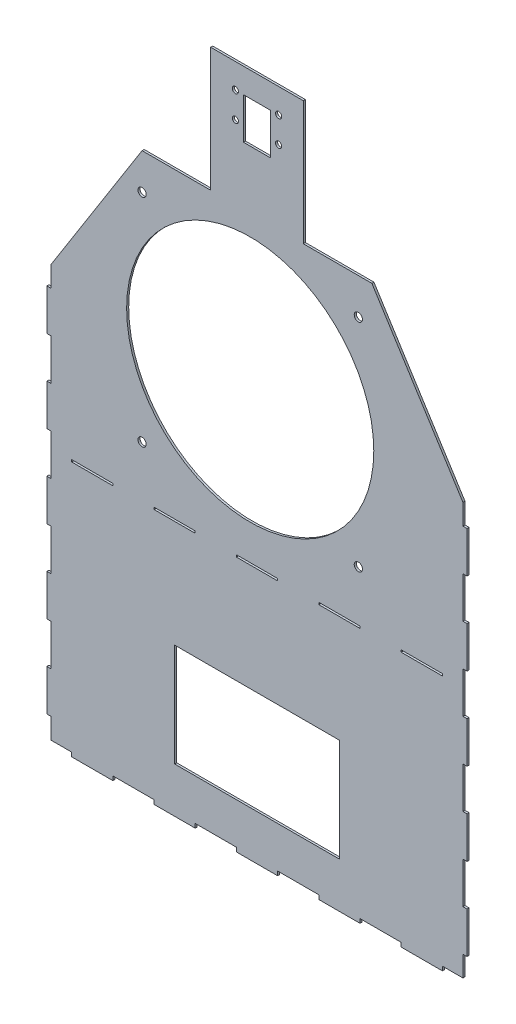
SolidWorks part; units mm, degrees
ref_plane "Přední rovina" through (0, 0, 0) normal (0, 0, 1) x (1, 0, 0)
ref_plane "Horní rovina" through (0, 0, 0) normal (0, 1, 0) x (1, 0, 0)
ref_plane "Pravá rovina" through (0, 0, 0) normal (1, 0, 0) x (0, 0, -1)
sketch "Skica1" plane through (0, 0, 0) normal (0, 0, 1) x (1, 0, 0)
  line L0 (-24.5981, -113.24) -> (-24.5981, -95.4761)
  line L1 (-124.5981, -113.24) -> (75.4019, -113.24)
  line L2 (-124.5981, -113.24) -> (-124.5981, 156.76)
  line L3 (-124.5981, 156.76) -> (75.4019, 156.76)
  line L4 (75.4019, -113.24) -> (75.4019, 156.76)
  line L5 (-114.5981, -113.24) -> (-94.5981, -113.24)
  line L6 (-114.5981, -113.24) -> (-114.5981, -115.24)
  line L7 (-114.5981, -115.24) -> (-94.5981, -115.24)
  line L8 (-94.5981, -113.24) -> (-94.5981, -115.24)
  line L9 (-74.5981, -113.24) -> (-54.5981, -113.24)
  line L10 (-74.5981, -113.24) -> (-74.5981, -115.24)
  line L11 (-74.5981, -115.24) -> (-54.5981, -115.24)
  line L12 (-54.5981, -113.24) -> (-54.5981, -115.24)
  line L13 (-34.5981, -113.24) -> (-14.5981, -113.24)
  line L14 (-34.5981, -113.24) -> (-34.5981, -115.24)
  line L15 (-34.5981, -115.24) -> (-14.5981, -115.24)
  line L16 (-14.5981, -113.24) -> (-14.5981, -115.24)
  line L17 (25.4019, -115.24) -> (5.4019, -115.24)
  line L18 (5.4019, -113.24) -> (5.4019, -115.24)
  line L19 (25.4019, -113.24) -> (5.4019, -113.24)
  line L20 (25.4019, -113.24) -> (25.4019, -115.24)
  line L21 (65.4019, -115.24) -> (45.4019, -115.24)
  line L22 (45.4019, -113.24) -> (45.4019, -115.24)
  line L23 (65.4019, -113.24) -> (45.4019, -113.24)
  line L24 (65.4019, -113.24) -> (65.4019, -115.24)
  line L25 (75.4019, 36.76) -> (77.4019, 36.76)
  line L26 (-124.5981, -103.24) -> (-126.5981, -103.24)
  line L27 (-124.5981, -103.24) -> (-124.5981, -83.24)
  line L28 (-124.5981, -83.24) -> (-126.5981, -83.24)
  line L29 (-126.5981, -103.24) -> (-126.5981, -83.24)
  line L30 (-124.5981, -63.24) -> (-126.5981, -63.24)
  line L31 (-124.5981, -63.24) -> (-124.5981, -43.24)
  line L32 (-124.5981, -43.24) -> (-126.5981, -43.24)
  line L33 (-126.5981, -63.24) -> (-126.5981, -43.24)
  line L34 (-124.5981, -23.24) -> (-126.5981, -23.24)
  line L35 (-124.5981, -23.24) -> (-124.5981, -3.24)
  line L36 (-124.5981, -3.24) -> (-126.5981, -3.24)
  line L37 (-126.5981, -23.24) -> (-126.5981, -3.24)
  line L38 (-124.5981, 16.76) -> (-126.5981, 16.76)
  line L39 (-124.5981, 16.76) -> (-124.5981, 36.76)
  line L40 (-124.5981, 36.76) -> (-126.5981, 36.76)
  line L41 (-126.5981, 16.76) -> (-126.5981, 36.76)
  line L42 (77.4019, 16.76) -> (77.4019, 36.76)
  line L43 (75.4019, 16.76) -> (77.4019, 16.76)
  line L44 (75.4019, 16.76) -> (75.4019, 36.76)
  line L45 (75.4019, -3.24) -> (77.4019, -3.24)
  line L46 (77.4019, -23.24) -> (77.4019, -3.24)
  line L47 (75.4019, -23.24) -> (77.4019, -23.24)
  line L48 (75.4019, -23.24) -> (75.4019, -3.24)
  line L49 (75.4019, -43.24) -> (77.4019, -43.24)
  line L50 (77.4019, -63.24) -> (77.4019, -43.24)
  line L51 (75.4019, -63.24) -> (77.4019, -63.24)
  line L52 (75.4019, -63.24) -> (75.4019, -43.24)
  line L53 (75.4019, -83.24) -> (77.4019, -83.24)
  line L54 (77.4019, -103.24) -> (77.4019, -83.24)
  line L55 (75.4019, -103.24) -> (77.4019, -103.24)
  line L56 (75.4019, -103.24) -> (75.4019, -83.24)
  line L57 (-80.3799, 156.76) -> (-124.5981, 86.76)
  line L58 (-114.5981, 9.76) -> (-94.5981, 9.76)
  line L59 (-114.5981, 9.76) -> (-114.5981, 8.76)
  line L60 (-114.5981, 8.76) -> (-94.5981, 8.76)
  line L61 (-94.5981, 9.76) -> (-94.5981, 8.76)
  line L62 (-74.5981, 9.76) -> (-54.5981, 9.76)
  line L63 (-74.5981, 9.76) -> (-74.5981, 8.76)
  line L64 (-74.5981, 8.76) -> (-54.5981, 8.76)
  line L65 (-54.5981, 9.76) -> (-54.5981, 8.76)
  line L66 (-34.5981, 9.76) -> (-14.5981, 9.76)
  line L67 (-34.5981, 9.76) -> (-34.5981, 8.76)
  line L68 (-34.5981, 8.76) -> (-14.5981, 8.76)
  line L69 (-14.5981, 9.76) -> (-14.5981, 8.76)
  line L70 (5.4019, 9.76) -> (25.4019, 9.76)
  line L71 (5.4019, 9.76) -> (5.4019, 8.76)
  line L72 (5.4019, 8.76) -> (25.4019, 8.76)
  line L73 (25.4019, 9.76) -> (25.4019, 8.76)
  line L74 (45.4019, 9.76) -> (65.4019, 9.76)
  line L75 (45.4019, 9.76) -> (45.4019, 8.76)
  line L76 (45.4019, 8.76) -> (65.4019, 8.76)
  line L77 (65.4019, 9.76) -> (65.4019, 8.76)
  line L78 (-124.5981, 56.76) -> (-126.5981, 56.76)
  line L79 (-124.5981, 56.76) -> (-124.5981, 76.76)
  line L80 (-124.5981, 76.76) -> (-126.5981, 76.76)
  line L81 (-126.5981, 56.76) -> (-126.5981, 76.76)
  line L82 (31.1836, 156.76) -> (75.4019, 86.76)
  line L83 (75.4019, 76.76) -> (77.4019, 76.76)
  line L84 (77.4019, 56.76) -> (77.4019, 76.76)
  line L85 (75.4019, 56.76) -> (77.4019, 56.76)
  line L86 (75.4019, 56.76) -> (75.4019, 76.76)
  line L88 (-47.0981, 156.76) -> (-2.0981, 156.76)
  line L89 (-47.0981, 156.76) -> (-47.0981, 216.8991)
  line L90 (-47.0981, 216.8991) -> (-2.0981, 216.8991)
  line L91 (-2.0981, 156.76) -> (-2.0981, 216.8991)
  line L92 (-31.0981, 204.8991) -> (-18.0981, 204.8991)
  line L93 (-31.0981, 204.8991) -> (-31.0981, 184.8991)
  line L94 (-31.0981, 184.8991) -> (-18.0981, 184.8991)
  line L95 (-18.0981, 204.8991) -> (-18.0981, 184.8991)
  line L96 (-64.5981, -93.24) -> (15.4019, -93.24)
  line L97 (-64.5981, -93.24) -> (-64.5981, -43.24)
  line L98 (-64.5981, -43.24) -> (15.4019, -43.24)
  line L99 (15.4019, -93.24) -> (15.4019, -43.24)
  circle A0 centre (-27.8799, 86.76) radius 60
  circle A1 centre (-80.3799, 139.26) radius 2
  circle A2 centre (24.6201, 139.26) radius 2
  circle A3 centre (24.6201, 34.26) radius 2
  circle A4 centre (-80.3799, 34.26) radius 2
  circle A5 centre (-35.0981, 204.8991) radius 1.5
  circle A6 centre (-14.0981, 204.8991) radius 1.5
  circle A7 centre (-14.0981, 192.3991) radius 1.5
  circle A8 centre (-35.0981, 192.3991) radius 1.5
  point P89 (-124.5981, 86.76)
  point P93 (-80.3799, 156.76)
  dimension "D3" = 120
  dimension "D4" = 70
  dimension "D6" = 4
  dimension "D7" = 4
  dimension "D8" = 4
  dimension "D9" = 4
  dimension "D35" = 3
  dimension "D36" = 3
  dimension "D37" = 3
  dimension "D38" = 3
  dimension "D1" = 270
  dimension "D2" = 200
  dimension "D5" = 105
  dimension "D10" = 105
  dimension "D11" = 52.5
  dimension "D12" = 52.5
  dimension "D13" = 20
  dimension "D14" = 20
  dimension "D15" = 20
  dimension "D16" = 20
  dimension "D17" = 10
  dimension "D18" = 20
  dimension "D19" = 2
  dimension "D20" = 10
  dimension "D21" = 20
  dimension "D22" = 20
  dimension "D23" = 20
  dimension "D24" = 20
  dimension "D25" = 20
  dimension "D26" = 20
  dimension "D27" = 20
  dimension "D28" = 2
  dimension "D29" = 1
  dimension "D30" = 20
  dimension "D31" = 20
  dimension "D32" = 10
  dimension "D33" = 7
  dimension "D34" = 45
  dimension "D39" = 12.5
  dimension "D40" = 21
  dimension "D41" = 12
  dimension "D42" = 12
  dimension "D43" = 12
  dimension "D44" = 13
  dimension "D45" = 4
  dimension "D46" = 20
  dimension "D47" = 22.5
  dimension "D48" = 50
  dimension "D49" = 80
  dimension "D50" = 20
  dimension "D51" = 40
extrude "Přidat vysunutím1" add sketch "Skica1" along normal blind 1 contours L8 L1 L6 L7 | L41 L38 L2 L40 | L37 L34 L2 L36 | L1 L4 L3 L2 A4 A3 A2 A1 A0 L58 L61 L60 L59 L62 L65 | L42 L25 L44 L43 | L46 L45 L48 L47 | L50 L49 L52 L51 | L54 L53 L56 L55 | L21 L22 L23 L24 | L17 L18 L19 L20 | L15 L16 L13 L14 | L11 L12 L9 L10 | L29 L28 L27 L26 | L33 L32 L31 L30 | L79 L78 L81 L80 | L83 L84 L85 L86 | L89 L88 L91 L90 | L93 L92 L95 L94 | A7 | A8 | A5 | A6 region at (-23.5464, 1.3679, 0) region at (-104.5981, -114.24, 0) region at (-125.5981, -13.24, 0) region at (-125.5981, 26.76, 0)
